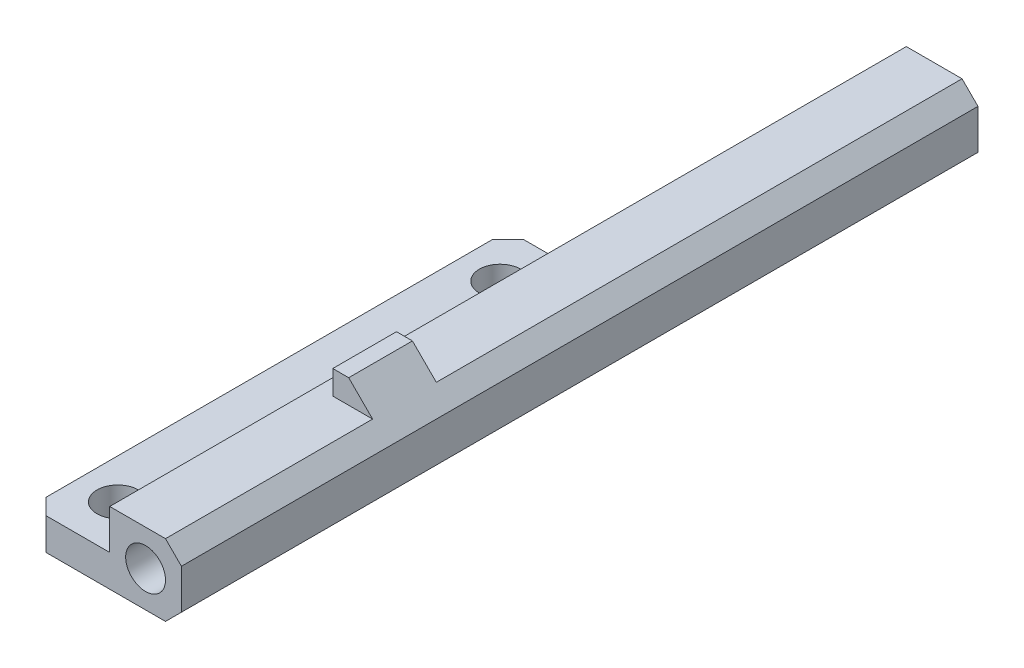
SolidWorks part; units mm, degrees
ref_plane "Front Plane" through (0, 0, 0) normal (0, 0, 1) x (1, 0, 0)
ref_plane "Top Plane" through (0, 0, 0) normal (0, 1, 0) x (1, 0, 0)
ref_plane "Right Plane" through (0, 0, 0) normal (1, 0, 0) x (0, 0, -1)
sketch "Sketch1" plane through (0, 0, 0) normal (0, 1, 0) x (1, 0, 0)
  line L1 (0, 0) -> (77.47, 0)
  line L2 (0, 0) -> (0, 127)
  line L3 (0, 127) -> (77.47, 127)
  line L4 (77.47, 0) -> (77.47, 127)
  dimension "D1" = 77.47
  dimension "D2" = 127
extrude "Boss-Extrude1" add sketch "Sketch1" along normal blind 11.43
sketch "Sketch2" plane through (0, 0, 0) normal (0, 0, 1) x (1, 0, 0)
  line L0 (5.715, 5.715) -> (71.755, 5.715) construction
  line L1 (38.735, 11.43) -> (38.735, 0) construction
  line L2 (0, 11.43) -> (77.47, 11.43) construction
  line L3 (0, 0) -> (77.47, 0) construction
  circle A0 centre (5.715, 5.715) radius 3.175
  circle A1 centre (71.755, 5.715) radius 3.175
  point P10 (38.735, 5.715)
  dimension "D1" = 6.35
  dimension "D2" = 66.04
extrude "Cut-Extrude1" cut sketch "Sketch2" against normal through all
sketch "Sketch3" plane through (0, 11.43, 0) normal (0, 1, 0) x (1, 0, 0)
  line L0 (11.43, 127) -> (11.43, 88.9)
  line L1 (77.47, 127) -> (0, 127) construction
  line L2 (11.43, 127) -> (66.04, 127)
  line L3 (66.04, 127) -> (66.04, 88.9)
  line L4 (53.34, 76.2) -> (24.13, 76.2)
  line L5 (0, 127) -> (0, 0) construction
  arc A0 (66.04, 88.9) -> (53.34, 76.2) centre (53.34, 88.9) cw
  arc A1 (24.13, 76.2) -> (11.43, 88.9) centre (24.13, 88.9) cw
  point P10 (38.735, 127)
  dimension "D1" = 12.7
  dimension "D2" = 11.43
  dimension "D3" = 50.8
extrude "Cut-Extrude2" cut sketch "Sketch3" against normal through all
sketch "Sketch4" plane through (0, 0, -127) normal (0, 0, -1) x (-1, 0, 0)
  line L0 (-11.43, 0) -> (-11.43, 11.43) construction
  line L1 (-66.04, 11.43) -> (-11.43, 11.43)
  line L2 (-66.04, 11.43) -> (-66.04, 5.08)
  line L3 (-66.04, 5.08) -> (-11.43, 5.08)
  line L4 (-11.43, 11.43) -> (-11.43, 5.08)
  line L5 (-11.43, 0) -> (0, 0) construction
  dimension "D1" = 5.08
extrude "Cut-Extrude3" cut sketch "Sketch4" against normal through all
chamfer "Chamfer1" distance 2.54 angle 45 4 edges at (0, 0, -63.5) (0, 11.43, -63.5) (77.47, 0, -63.5) (77.47, 11.43, -63.5)
sketch "Sketch5" plane through (0, 11.43, 0) normal (0, 1, 0) x (1, 0, 0)
  line L0 (66.04, 76.2) -> (0, 76.2)
  line L1 (66.04, 0) -> (66.04, 88.9) construction
  line L2 (0, 0) -> (0, 127) construction
  line L3 (0, 76.2) -> (0, 127)
  line L4 (0, 127) -> (66.04, 127)
  line L5 (66.04, 127) -> (66.04, 76.2)
  line L6 (24.13, 76.2) -> (53.34, 76.2) construction
extrude "Cut-Extrude4" cut sketch "Sketch5" against normal through all
sketch "Sketch6" plane through (0, 11.43, 0) normal (0, 1, 0) x (1, 0, 0)
  line L0 (53.34, 76.2) -> (53.34, 0)
  line L1 (11.43, 76.2) -> (66.04, 76.2) construction
  line L2 (66.04, 0) -> (11.43, 0) construction
  line L3 (53.34, 0) -> (0, 0)
  line L4 (0, 0) -> (0, 76.2)
  line L5 (0, 76.2) -> (53.34, 76.2)
  line L6 (66.04, 0) -> (66.04, 127) construction
  dimension "D1" = 12.7
extrude "Cut-Extrude5" cut sketch "Sketch6" against normal through all
sketch "Sketch7" plane through (0, 5.08, 0) normal (0, 1, 0) x (1, 0, 0)
  line L0 (53.34, 76.2) -> (66.04, 76.2) construction
  circle A0 centre (59.69, 68.58) radius 3.302
  circle A4 centre (59.69, 7.62) radius 3.302
  point P4 (59.69, 76.2)
  point P5 (0, 0)
  point P13 (0, 0)
  dimension "D1" = 6.604
  dimension "D2" = 7.62
  dimension "D3" = 68.58
extrude "Cut-Extrude6" cut sketch "Sketch7" against normal through all
chamfer "Chamfer2" distance 2.54 angle 45 2 edges at (53.34, 2.54, -76.2) (53.34, 2.54, 0)
ref_plane "Plane2" through (0, 0, -38.1) normal (0, 0, 1) x (1, 0, 0)
sketch "Sketch8" plane through (0, 0, -38.1) normal (0, 0, 1) x (1, 0, 0)
  line L0 (74.93, 11.43) -> (71.12, 15.24)
  line L1 (71.12, 15.24) -> (68.58, 15.24)
  line L2 (68.58, 15.24) -> (68.58, 11.43)
  line L4 (68.58, 11.43) -> (74.93, 11.43)
  line L5 (66.04, 11.43) -> (74.93, 11.43) construction
  point P3 (0, 0)
  point P8 (0, 0)
  dimension "D1" = 45
  dimension "D3" = 3.81
extrude "Boss-Extrude2" add sketch "Sketch8" along normal blind 5.08
mirror "Mirror1" about plane through (0, 0, -38.1) normal (0, 0, 1) of "Boss-Extrude2"
